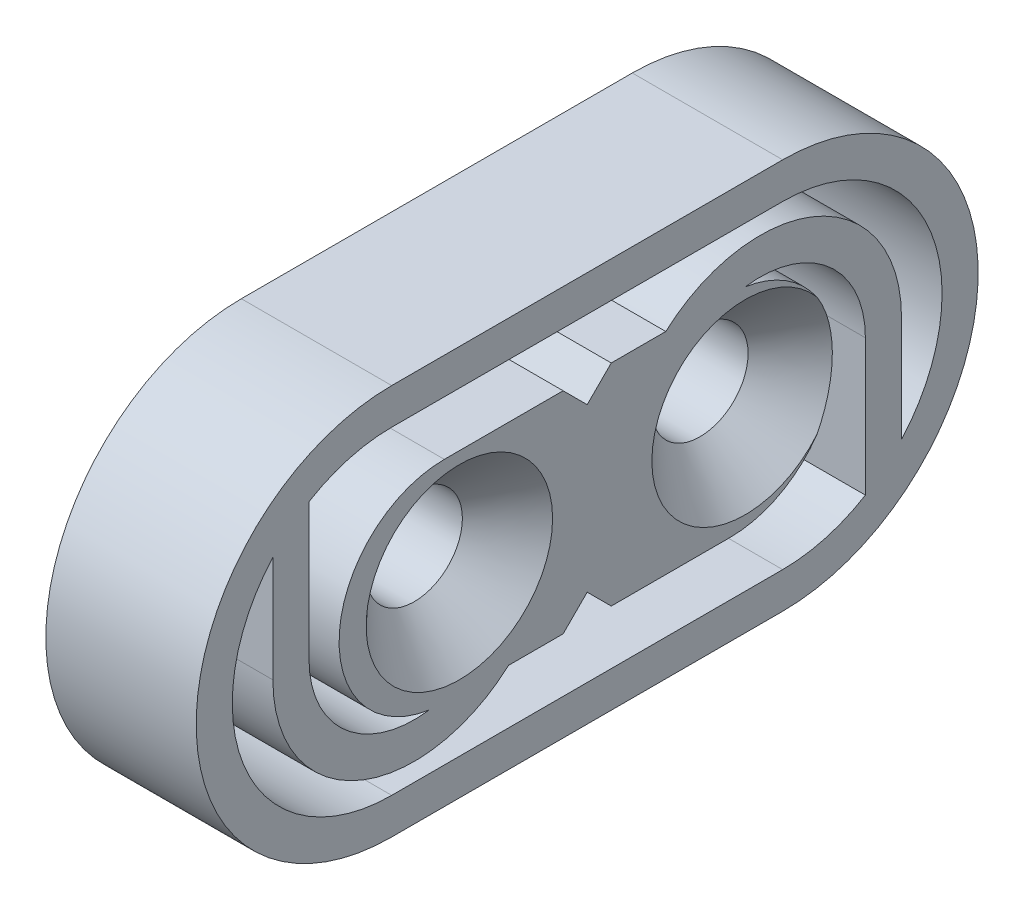
SolidWorks part; units mm, degrees
material "PVC 0.007 Plasticized"
ref_plane "Front Plane" through (0, 0, 0) normal (1, 0, 0) x (0, 1, 0)
ref_plane "Top Plane" through (0, 0, 0) normal (0, 0, 1) x (0, 1, 0)
ref_plane "Right Plane" through (0, 0, 0) normal (0, 1, 0) x (-1, 0, 0)
sketch "Sketch2" plane through (0, 0, 0) normal (1, 0, 0) x (0, 1, 0)
  line L0 (-6.4721, 6.4962) -> (-6.4721, -6.5038)
  line L1 (-5.2721, 6.4962) -> (-5.2721, -6.5038)
  line L2 (0.0279, 10.4462) -> (3.5616, 10.4462)
  line L3 (4.5586, 9.2462) -> (0.0279, 9.2462)
  line L4 (-3.4721, 2.6094) -> (-3.4721, 0.7962)
  line L5 (-3.4721, 0.7962) -> (-2.6721, -0.0038)
  line L6 (-2.6721, -0.0038) -> (-3.4721, -0.8038)
  line L7 (-3.4721, -0.8038) -> (-3.4721, -4.7538)
  line L8 (3.5279, -2.6169) -> (3.5279, -0.8038)
  line L9 (3.5279, -0.8038) -> (2.7279, -0.0038)
  line L10 (2.7279, -0.0038) -> (3.5279, 0.7962)
  line L11 (3.5279, 0.7962) -> (3.5279, 4.7462)
  line L12 (5.3279, 6.4962) -> (5.3279, -6.5038)
  line L13 (6.5279, 6.4962) -> (6.5279, -6.5038)
  line L14 (-3.5059, -10.4538) -> (0.0279, -10.4538)
  line L15 (-4.5029, -9.2538) -> (0.0279, -9.2538)
  arc A0 (3.5279, 4.7462) -> (-3.4362, 5.2462) centre (0.0279, 4.7462) ccw
  arc A1 (0.0279, 10.4462) -> (-3.4721, 2.6094) centre (0.0279, 5.7462) ccw
  arc A2 (-6.4721, -6.5038) -> (6.5279, -6.5038) centre (0.0279, -6.5038) ccw
  arc A3 (-5.2721, -6.5038) -> (-4.5029, -9.2538) centre (0.0279, -6.5038) ccw
  arc A4 (5.3279, 6.4962) -> (4.5586, 9.2462) centre (0.0279, 6.4962) ccw
  arc A5 (6.5279, 6.4962) -> (-6.4721, 6.4962) centre (0.0279, 6.4962) ccw
  arc A6 (0.0279, -9.2538) -> (3.492, -5.2538) centre (0.0279, -5.7538) ccw
  arc A7 (0.0279, -10.4538) -> (3.5279, -2.6169) centre (0.0279, -5.7538) ccw
  arc A8 (-3.4721, -4.7538) -> (3.492, -5.2538) centre (0.0279, -4.7538) ccw
  arc A9 (0.0279, 9.2462) -> (-3.4362, 5.2462) centre (0.0279, 5.7462) ccw
  arc A10 (-3.5059, -10.4538) -> (5.3279, -6.5038) centre (0.0279, -6.5038) ccw
  arc A11 (3.5616, 10.4462) -> (-5.2721, 6.4962) centre (0.0279, 6.4962) ccw
extrude "Boss-Extrude2" add sketch "Sketch2" along normal blind 5
sketch "Sketch4" plane through (5, 0, 0) normal (1, 0, 0) x (0, 1, 0)
  line L0 (-2.6721, -0.0038) -> (2.7279, -0.0038) construction
  line L1 (0.0279, 8.2462) -> (0.0279, -8.2538) construction
  circle A0 centre (0.0279, 4.2462) radius 1.6
  circle A1 centre (0.0279, -5.2538) radius 1.6
  arc A2 (3.5279, 4.7462) -> (-3.4362, 5.2462) centre (0.0279, 4.7462) ccw construction
  arc A3 (-3.4721, -4.7538) -> (3.492, -5.2538) centre (0.0279, -4.7538) ccw construction
  dimension "D1" = 3.2
  dimension "D2" = 3.2
  dimension "D3" = 9.5
  dimension "D4" = 5.25
extrude "Cut-Extrude1" cut sketch "Sketch4" against normal blind 10
chamfer "Chamfer1" distance 1.5 angle 45 2 edges at (5, 0.0279, 2.6462) (5, 0.0279, -6.8538)
